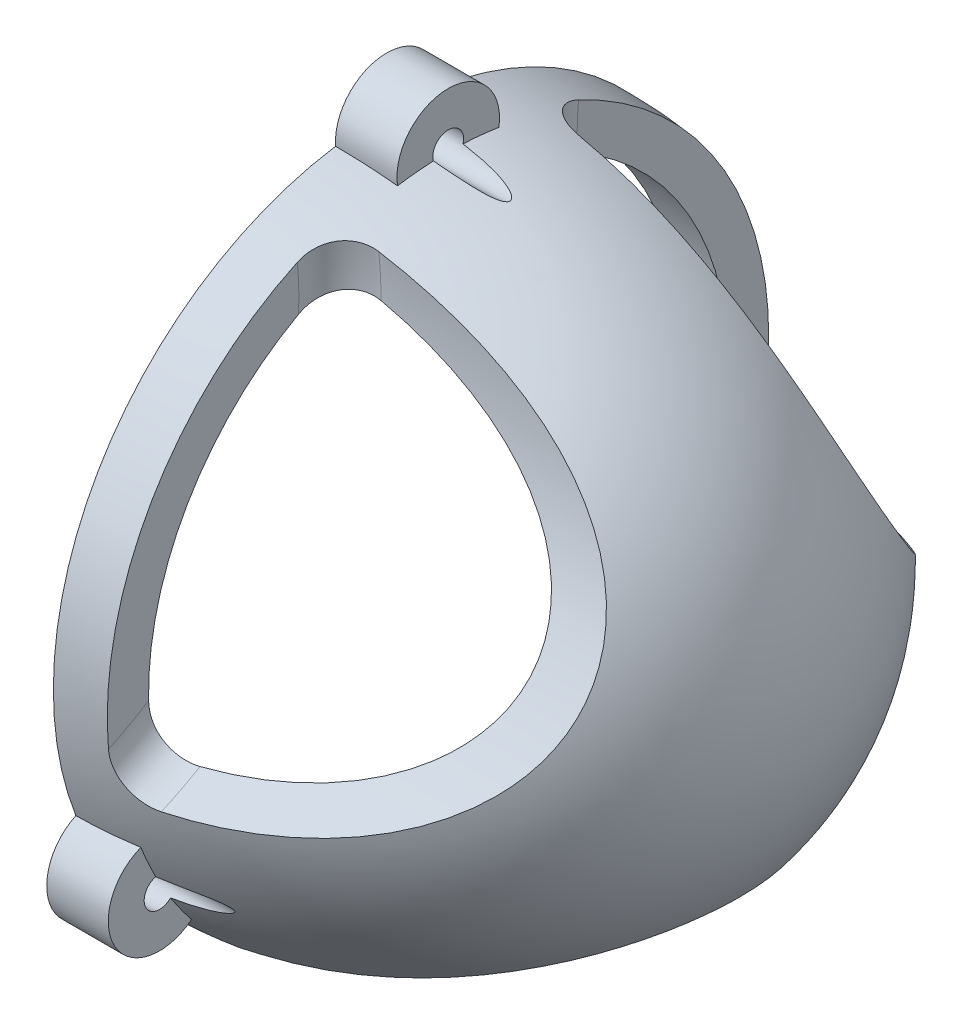
SolidWorks part; units mm, degrees
material "ABS"
ref_plane "Alzado" through (0, 0, 0) normal (0, 0, 1) x (1, 0, 0)
ref_plane "Planta" through (0, 0, 0) normal (0, 1, 0) x (1, 0, 0)
ref_plane "Vista lateral" through (0, 0, 0) normal (1, 0, 0) x (0, 0, -1)
sketch "Croquis1" plane through (0, 0, 0) normal (0, 0, 1) x (1, 0, 0)
  line L0 (0, 0) -> (0, -32.5)
  line L1 (40, 0) -> (0, 0)
  ellipse E0 centre (0, 0) end of major axis (40, 0) minor radius 32.5 (0, -32.5) -> (40, 0) ccw
  dimension "D1" = 80
  dimension "D2" = 65
revolve "Revolución1" add sketch "Croquis1" angle 360 about L1
shell "Vaciado1" thickness 4 removed face at (0, 0, -32.5)
ref_plane "Plano1" through (5, 0, 0) normal (1, 0, 0) x (0, 0, -1)
sketch "Croquis2" plane through (5, 0, 0) normal (1, 0, 0) x (0, 0, -1)
  line L1 (0, 32.5) -> (-28.1458, -16.25)
  line L2 (-28.1458, -16.25) -> (28.1458, -16.25)
  line L3 (28.1458, -16.25) -> (0, 32.5)
  circle A0 centre (0, 0) radius 32.5
  circle A2 centre (0, 0) radius 16.25 construction
  circle A3 centre (0, 32.5) radius 10
  circle A4 centre (28.1458, -16.25) radius 10
  circle A5 centre (-28.1458, -16.25) radius 10
  arc A6 (9.8809, 30.9615) -> (31.754, -6.9236) centre (45.3703, 26.1946) ccw
  arc A7 (-9.8809, 30.9615) -> (-31.754, -6.9236) centre (-45.3703, 26.1946) cw
  arc A8 (-21.873, -24.0379) -> (21.873, -24.0379) centre (0, -52.3891) cw
  dimension "D1" = 65
  dimension "D2" = 20
  dimension "D3" = 20
  dimension "D4" = 20
extrude "Cortar-Extruir1" cut sketch "Croquis2" along normal through all contours A7 A0 | A0 A6 | A8 A0 region at (5, 12.2293, -21.1817) region at (5, 12.2293, 21.1817) region at (5, -24.4585, 0)
sketch "Croquis3" plane through (0, 0, 0) normal (1, 0, 0) x (0, 0, -1)
  line L0 (3.6756, 29.1103) -> (-3.6756, 29.1103)
  line L1 (0, 32.5) -> (-28.1458, -16.25)
  line L2 (-28.1458, -16.25) -> (28.1458, -16.25)
  line L3 (28.1458, -16.25) -> (0, 32.5)
  line L4 (27.2601, -11.3291) -> (23.6478, -18.4336)
  line L5 (-28.1458, -11.25) -> (-23.6478, -18.4336)
  circle A0 centre (0, 0) radius 16.25 construction
  circle A1 centre (0, 32.5) radius 5
  circle A2 centre (-28.1458, -16.25) radius 5
  circle A3 centre (28.1458, -16.25) radius 5
  dimension "D1" = 10
  dimension "D2" = 10
  dimension "D3" = 10
extrude "Saliente-Extruir2" add sketch "Croquis3" along normal blind 6 contours L0 A1 L1 L3 | L4 A3 L3 L2 | L5 A2 L2 L1 | L3 L4 L2 | L5 L1 L2 | L0 L3 L1 region at (0, 33.2548, 0) region at (0, 30.2402, 0) region at (0, -16.6456, -28.8971) region at (0, -15.21, -26.4161) region at (0, -15.3829, 26.6016) region at (0, -16.754, 28.9615)
sketch "Croquis4" plane through (0, 0, 0) normal (-1, 0, 0) x (0, 0, 1)
  circle A0 centre (0, 32.5) radius 1.5
  circle A1 centre (28.1458, -16.25) radius 1.5
  circle A2 centre (-28.1458, -16.25) radius 1.5
  dimension "D1" = 3
  dimension "D2" = 3
  dimension "D3" = 3
extrude "Cortar-Extruir2" cut sketch "Croquis4" against normal blind 15
fillet "Redondeo1" radius 4 6 edges at (5, -22.6694, -19.9739) (5, -22.6694, 19.9739) (5, -5.9632, -29.6192) (5, 28.6326, -9.6453) (5, -5.9632, 29.6192) (5, 28.6326, 9.6453)
